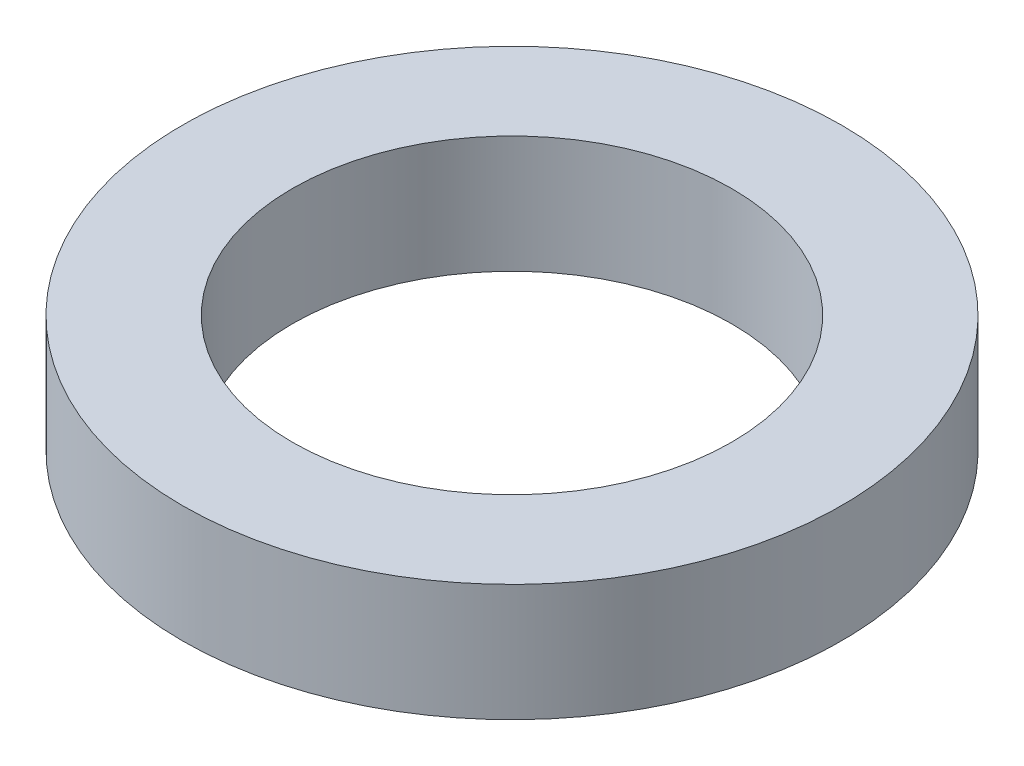
SolidWorks part; units mm, degrees
ref_plane "Front Plane" through (0, 0, 0) normal (0, 0, 1) x (1, 0, 0)
ref_plane "Top Plane" through (0, 0, 0) normal (0, 1, 0) x (1, 0, 0)
ref_plane "Right Plane" through (0, 0, 0) normal (1, 0, 0) x (0, 0, -1)
sketch "Sketch1" plane through (0, 0, 0) normal (0, 1, 0) x (1, 0, 0)
  circle A0 centre (0, 0) radius 45
  dimension "FLANGE_OD" = 90
extrude "Boss-Extrude1" add sketch "Sketch1" along normal blind 16
sketch "Sketch2" plane through (0, 0, 0) normal (0, 1, 0) x (1, 0, 0)
  circle A0 centre (0, 0) radius 30
  dimension "BORE_D" = 60
extrude "Cut-Extrude1" cut sketch "Sketch2" along normal through all
sketch "Sketch3" plane through (0, 16, 0) normal (0, 1, 0) x (1, 0, 0)
  circle A0 centre (0, 0) radius 17.7748 construction
  circle A1 centre (-17.7748, 0) radius 2.6721
  dimension "BOLT_D" = 5.3442
  dimension "BOLT_PCD" = 35.5496
extrude "Cut-Extrude2" cut sketch "Sketch3" against normal blind 15.2394 rebuild error yes
pattern_circular "CirPattern1" count 5 over 360 rebuild error yes
